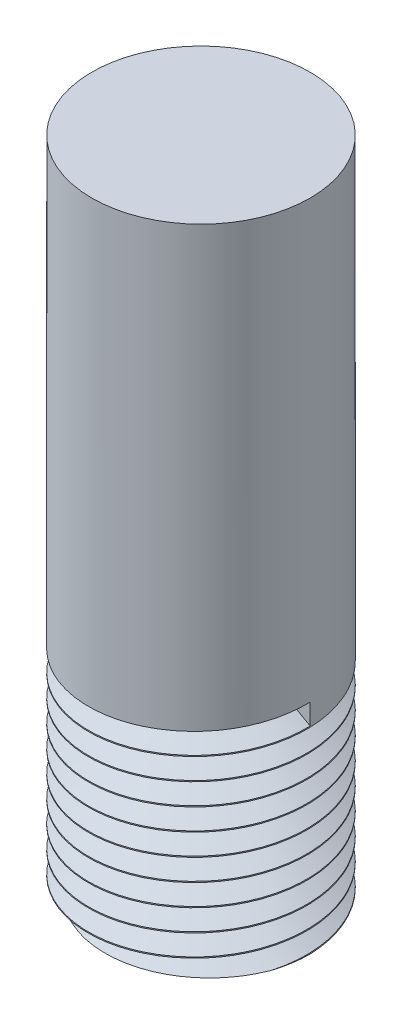
SolidWorks part; units mm, degrees
ref_plane "Front Plane" through (0, 0, 0) normal (0, 0, 1) x (1, 0, 0)
ref_plane "Top Plane" through (0, 0, 0) normal (0, 1, 0) x (1, 0, 0)
ref_plane "Right Plane" through (0, 0, 0) normal (1, 0, 0) x (0, 0, -1)
sketch "Sketch1" plane through (0, 0, 0) normal (0, 1, 0) x (1, 0, 0)
  circle A0 centre (0, 0) radius 5
extrude "Boss-Extrude1" add sketch "Sketch1" along normal blind 30
sketch "Sketch4" plane through (0, 0, 0) normal (0, 1, 0) x (1, 0, 0)
  circle A0 centre (0, 0) radius 5
curve "Helix/Spiral1" pitch 1 height 10 radius 5 centre (0, 0, 0) axis (0, 1, 0) start towards (1, 0, 0)
sketch "Sketch5" plane through (0, 0, 0) normal (0, 0, 1) x (1, 0, 0)
  line L0 (5, 0) -> (5, -0.95)
  line L1 (5.5, 0) -> (-5.5, 0) construction
  line L7 (5, 0) -> (4.1773, -0.475)
  line L8 (4.1773, -0.475) -> (5, -0.95)
  spline S0 degree 3 poles (5, 0) (5, 0.0207) (4.7397, 0.0626) (3.6276, 0.125) (1.9632, 0.1875) (0, 0.25) (-1.9632, 0.3125) (-3.6276, 0.375) (-4.7397, 0.4375) (-5.1302, 0.5) (-4.7397, 0.5625) (-3.6276, 0.625) (-1.9632, 0.6875) (0, 0.75) (1.9632, 0.8125) (3.6276, 0.875) (4.7397, 0.9375) (5.1302, 1) (4.7397, 1.0625) (3.6276, 1.125) (1.9632, 1.1875) (0, 1.25) (-1.9632, 1.3125) (-3.6276, 1.375) (-4.7397, 1.4375) (-5.1302, 1.5) (-4.7397, 1.5625) (-3.6276, 1.625) (-1.9632, 1.6875) (0, 1.75) (1.9632, 1.8125) (3.6276, 1.875) (4.7397, 1.9375) (5.1302, 2) (4.7397, 2.0625) (3.6276, 2.125) (1.9632, 2.1875) (0, 2.25) (-1.9632, 2.3125) (-3.6276, 2.375) (-4.7397, 2.4375) (-5.1302, 2.5) (-4.7397, 2.5625) (-3.6276, 2.625) (-1.9632, 2.6875) (0, 2.75) (1.9632, 2.8125) (3.6276, 2.875) (4.7397, 2.9375) (5.1302, 3) (4.7397, 3.0625) (3.6276, 3.125) (1.9632, 3.1875) (0, 3.25) (-1.9632, 3.3125) (-3.6276, 3.375) (-4.7397, 3.4375) (-5.1302, 3.5) (-4.7397, 3.5625) (-3.6276, 3.625) (-1.9632, 3.6875) (0, 3.75) (1.9632, 3.8125) (3.6276, 3.875) (4.7397, 3.9375) (5.1302, 4) (4.7397, 4.0625) (3.6276, 4.125) (1.9632, 4.1875) (0, 4.25) (-1.9632, 4.3125) (-3.6276, 4.375) (-4.7397, 4.4375) (-5.1302, 4.5) (-4.7397, 4.5625) (-3.6276, 4.625) (-1.9632, 4.6875) (0, 4.75) (1.9632, 4.8125) (3.6276, 4.875) (4.7397, 4.9375) (5.1302, 5) (4.7397, 5.0625) (3.6276, 5.125) (1.9632, 5.1875) (0, 5.25) (-1.9632, 5.3125) (-3.6276, 5.375) (-4.7397, 5.4375) (-5.1302, 5.5) (-4.7397, 5.5625) (-3.6276, 5.625) (-1.9632, 5.6875) (0, 5.75) (1.9632, 5.8125) (3.6276, 5.875) (4.7397, 5.9375) (5.1302, 6) (4.7397, 6.0625) (3.6276, 6.125) (1.9632, 6.1875) (0, 6.25) (-1.9632, 6.3125) (-3.6276, 6.375) (-4.7397, 6.4375) (-5.1302, 6.5) (-4.7397, 6.5625) (-3.6276, 6.625) (-1.9632, 6.6875) (0, 6.75) (1.9632, 6.8125) (3.6276, 6.875) (4.7397, 6.9375) (5.1302, 7) (4.7397, 7.0625) (3.6276, 7.125) (1.9632, 7.1875) (0, 7.25) (-1.9632, 7.3125) (-3.6276, 7.375) (-4.7397, 7.4375) (-5.1302, 7.5) (-4.7397, 7.5625) (-3.6276, 7.625) (-1.9632, 7.6875) (0, 7.75) (1.9632, 7.8125) (3.6276, 7.875) (4.7397, 7.9375) (5.1302, 8) (4.7397, 8.0625) (3.6276, 8.125) (1.9632, 8.1875) (0, 8.25) (-1.9632, 8.3125) (-3.6276, 8.375) (-4.7397, 8.4375) (-5.1302, 8.5) (-4.7397, 8.5625) (-3.6276, 8.625) (-1.9632, 8.6875) (0, 8.75) (1.9632, 8.8125) (3.6276, 8.875) (4.7397, 8.9375) (5.1302, 9) (4.7397, 9.0625) (3.6276, 9.125) (1.9632, 9.1875) (0, 9.25) (-1.9632, 9.3125) (-3.6276, 9.375) (-4.7397, 9.4375) (-5.1302, 9.5) (-4.7397, 9.5625) (-3.6276, 9.625) (-1.9632, 9.6875) (0, 9.75) (1.9632, 9.8125) (3.6276, 9.875) (4.7397, 9.9374) (5, 9.9793) (5, 10) knots 0 0 0 0 0.00625 0.0125 0.01875 0.025 0.03125 0.0375 0.04375 0.05 0.05625 0.0625 0.06875 0.075 0.08125 0.0875 0.09375 0.1 0.10625 0.1125 0.11875 0.125 0.13125 0.1375 0.14375 0.15 0.15625 0.1625 0.16875 0.175 0.18125 0.1875 0.19375 0.2 0.20625 0.2125 0.21875 0.225 0.23125 0.2375 0.24375 0.25 0.25625 0.2625 0.26875 0.275 0.28125 0.2875 0.29375 0.3 0.30625 0.3125 0.31875 0.325 0.33125 0.3375 0.34375 0.35 0.35625 0.3625 0.36875 0.375 0.38125 0.3875 0.39375 0.4 0.40625 0.4125 0.41875 0.425 0.43125 0.4375 0.44375 0.45 0.45625 0.4625 0.46875 0.475 0.48125 0.4875 0.49375 0.5 0.50625 0.5125 0.51875 0.525 0.53125 0.5375 0.54375 0.55 0.55625 0.5625 0.56875 0.575 0.58125 0.5875 0.59375 0.6 0.60625 0.6125 0.61875 0.625 0.63125 0.6375 0.64375 0.65 0.65625 0.6625 0.66875 0.675 0.68125 0.6875 0.69375 0.7 0.70625 0.7125 0.71875 0.725 0.73125 0.7375 0.74375 0.75 0.75625 0.7625 0.76875 0.775 0.78125 0.7875 0.79375 0.8 0.80625 0.8125 0.81875 0.825 0.83125 0.8375 0.84375 0.85 0.85625 0.8625 0.86875 0.875 0.88125 0.8875 0.89375 0.9 0.90625 0.9125 0.91875 0.925 0.93125 0.9375 0.94375 0.95 0.95625 0.9625 0.96875 0.975 0.98125 0.9875 0.99375 1 1 1 1 construction
  point P6 (4.2311, -0.475)
  point P10 (0, 0)
  dimension "D1" = 0.95
  dimension "D2" = 0.95
  dimension "D3" = 0.95
sweep "Cut-Sweep1" cut profiles "Sketch5" path "Helix/Spiral1" align with end faces yes
